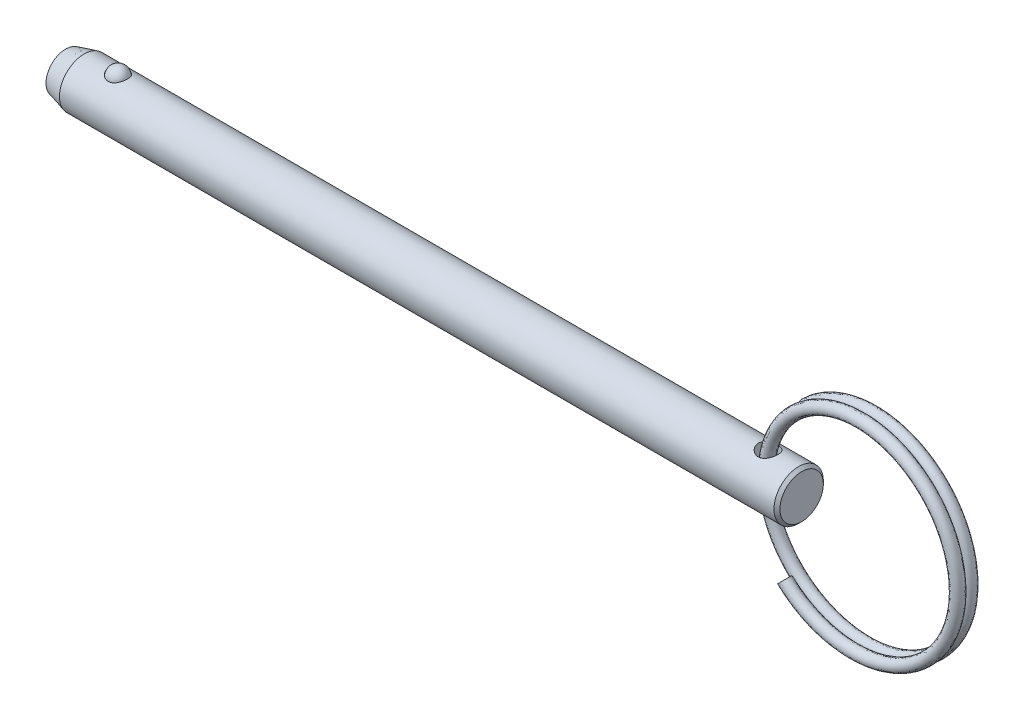
SolidWorks part; units mm, degrees
ref_plane "Front" through (0, 0, 0) normal (0, 0, 1) x (1, 0, 0)
ref_plane "Top" through (0, 0, 0) normal (0, 1, 0) x (1, 0, 0)
ref_plane "Right" through (0, 0, 0) normal (1, 0, 0) x (0, 0, -1)
sketch "Sketch1" plane through (0, 0, 0) normal (0, 0, 1) x (1, 0, 0)
  line L0 (5.588, 2.794) -> (5.207, 3.175)
  line L1 (5.207, 3.175) -> (5.588, 3.175) construction
  line L4 (5.588, 2.794) -> (5.588, 0)
  line L5 (5.588, 3.175) -> (5.588, 2.794) construction
  line L16 (5.207, 3.175) -> (-86.8349, 3.175)
  line L17 (-89.2048, 3.175) -> (-89.2048, 2.54) construction
  line L19 (-86.8349, 3.175) -> (-89.2048, 3.175) construction
  line L22 (-89.2048, -3.175) -> (-86.8349, -3.175) construction
  line L23 (-82.4703, 2.8575) -> (-82.4703, -2.8575) construction
  line L24 (-89.2048, 0) -> (5.588, 0)
  line L27 (5.588, 0) -> (8.382, 0) construction
  line L29 (-89.2048, 0) -> (-89.2048, -2.54) construction
  line L36 (0, 0) -> (0, 3.175) construction
  line L37 (-89.2048, 2.54) -> (-89.2048, 0)
  line L38 (-86.8349, -3.175) -> (5.588, -3.175) construction
  line L39 (-89.2048, -2.54) -> (-89.2048, -3.175) construction
  line L40 (-86.8349, 3.175) -> (-89.2048, 2.54)
  line L42 (-86.8349, -3.175) -> (-89.2048, -2.54) construction
  line L43 (-86.8349, 3.175) -> (-86.8349, -3.175) construction
  circle A2 centre (-82.4703, 2.8575) radius 1.2319 construction
  point P35 (-81.28, 3.175)
  dimension "D2" = 5.715
  dimension "D11" = 0.9144
  dimension "A" = 6.35
  dimension "D" = 5.588
  dimension "E" = 7.2644
  dimension "D3" = 0.381
  dimension "Useable Length" = 81.28
  dimension "D12" = 5.08
  dimension "C" = 7.9248
  dimension "A1" = 15
revolve "Revolve1" add sketch "Sketch1" angle 360 about L27
sketch "Sketch2" plane through (0, 0, 0) normal (0, 0, 1) x (1, 0, 0)
  line L0 (-81.213, 2.8575) -> (-83.7276, 2.8575)
  line L1 (-82.4703, 4.0894) -> (-82.4703, 4.1148) construction
  line L2 (-81.213, 2.8575) -> (-78.6984, 2.8575) construction
  circle A0 centre (-82.4703, 2.8575) radius 1.2319 construction
  circle A1 centre (-82.4703, 2.8575) radius 1.2319 construction
  arc A2 (-83.7276, 2.8575) -> (-81.213, 2.8575) centre (-82.4703, 2.8575) cw
  dimension "D1" = 0.0254
revolve "Cut-Revolve1" cut sketch "Sketch2" angle 360 about L2
sketch "Sketch3" plane through (0, 0, 0) normal (0, 0, 1) x (1, 0, 0)
  line L0 (-81.2384, 2.8575) -> (-83.7022, 2.8575)
  line L1 (-81.2384, 2.8575) -> (-78.7746, 2.8575) construction
  circle A0 centre (-82.4703, 2.8575) radius 1.2319 construction
  arc A1 (-81.2384, 2.8575) -> (-83.7022, 2.8575) centre (-82.4703, 2.8575) ccw
revolve "Revolve2" add sketch "Sketch3" angle 360 about L1
sketch "Sketch4" plane through (0, 0, 0) normal (0, 0, 1) x (1, 0, 0)
  line L1 (1.27, -3.175) -> (2.54, -3.175)
  line L2 (1.27, -3.175) -> (1.27, 3.175)
  line L3 (1.27, 3.175) -> (2.54, 3.175)
  line L4 (2.54, -3.175) -> (2.54, 3.175)
  line L5 (1.27, -3.175) -> (1.27, -4.445) construction
  line L6 (2.54, 3.175) -> (5.588, 3.175) construction
  line L8 (0, -3.175) -> (0, 3.175) construction
  line L9 (0, 0) -> (1.27, 0) construction
  line L11 (1.27, 0) -> (2.54, 0) construction
  line L12 (5.207, 3.175) -> (-86.8349, 3.175) construction
  line L14 (-86.8349, -3.175) -> (5.588, -3.175) construction
  dimension "D1" = 2.54
revolve "Cut-Revolve2" cut sketch "Sketch4" angle 360 about L2
sketch "Sketch5" plane through (0, 0, 0) normal (0, 0, 1) x (1, 0, 0)
  line L0 (0, 0) -> (0.293, 0) construction
  line L1 (0.293, 0) -> (0.293, 3.175) construction
  line L2 (5.207, 3.175) -> (-86.8349, 3.175) construction
  line L3 (13.755, 0) -> (27.217, 0) construction
  line L4 (2.54, 3.175) -> (2.247, 3.175) construction
  line L5 (1.27, 3.175) -> (2.54, 3.175) construction
  line L6 (0.6728, 3.175) -> (0.6728, -3.175) construction
  line L7 (0.293, 3.175) -> (0, 3.175) construction
  line L8 (1.27, -3.175) -> (2.54, -3.175) construction
  line L9 (0.6728, -3.175) -> (2.54, -3.175) construction
  line L10 (0.293, 0) -> (13.755, 0) construction
  line L11 (13.755, 0) -> (8.7098, -10.8195) construction
  line L12 (2.247, 3.175) -> (0.6728, 3.175) construction
  line L13 (13.755, 11.938) -> (13.755, 13.462) construction
  line L14 (8.7098, -10.8195) -> (8.3878, -11.5101) construction
  circle A0 centre (13.755, 0) radius 13.462
  circle A1 centre (13.755, 0) radius 11.938 construction
  circle A2 centre (13.755, 0) radius 12.7 construction
  point P26 (13.755, 12.7)
  dimension "D1" = 65
  dimension "R Ring Dia" = 25.4
  dimension "Ring OD" = 1.524
curve "Helix/Spiral1" pitch 1.5494 height 1.3557 radius 13.462 left hand yes centre (13.755, 0, 0) axis (0, 0, -1) start towards (1, 0, 0)
sketch "Sketch6" plane through (114.0038, 0, 0) normal (0, 1, 0) x (0, 0, -1)
  line L0 (0, 112.1868) -> (0, 112.9488) construction
  line L1 (0, 112.9488) -> (0, 113.7108) construction
  circle A0 centre (0, 112.9488) radius 0.762
  dimension "D1" = 1.524
sketch "Sketch7" plane through (0, 0, 0) normal (0, 0, 1) x (1, 0, 0)
  circle A0 centre (13.755, 0) radius 13.462 construction
  circle A1 centre (13.755, 0) radius 13.462
curve "Helix/Spiral2" pitch 1.5494 height 1.3557 radius 13.462 left hand yes centre (13.755, 0, 0) axis (0, 0, 1) start towards (1, 0, 0)
sweep "Sweep1" add profiles "Sketch6" path "Helix/Spiral1"
sweep "Sweep2" add profiles "Sketch6<2>" path "Helix/Spiral2"
sketch "Sketch6<2>" plane through (114.0038, 0, 0) normal (0, 1, 0) x (0, 0, -1) same geometry as "Sketch6"
ref_plane "Plane1" through (0, -10.8195, 0) normal (0, 1, 0) x (-1, 0, 0)
sketch "Sketch8" plane through (0, -10.8195, 0) normal (0, 1, 0) x (-1, 0, 0)
  line L0 (296.0902, 0) -> (-8.7098, 0) construction
  line L1 (10.3402, -0.7779) -> (4.5066, -0.7779)
  line L2 (3.5004, -0.9415) -> (-7.2005, -4.517)
  line L3 (-7.2005, 4.517) -> (3.5004, 0.9415)
  line L4 (4.5066, 0.7779) -> (282.8738, 0.7779)
  line L5 (283.88, 0.9415) -> (294.5809, 4.517)
  line L6 (277.0402, -0.7779) -> (282.8738, -0.7779)
  line L7 (283.88, -0.9415) -> (294.5809, -4.517)
  line L8 (10.3402, -0.7779) -> (10.3402, 0.7779) construction
  arc A0 (-7.2005, 4.517) -> (-7.2005, -4.517) centre (-8.7098, 0) ccw
  arc A1 (294.5809, -4.517) -> (294.5809, 4.517) centre (296.0902, 0) ccw
  arc A2 (4.5066, -0.7779) -> (3.5004, -0.9415) centre (4.5066, -3.9529) ccw
  arc A3 (3.5004, 0.9415) -> (4.5066, 0.7779) centre (4.5066, 3.9529) ccw
  arc A4 (282.8738, -0.7779) -> (283.88, -0.9415) centre (282.8738, -3.9529) cw
  arc A5 (282.8738, 0.7779) -> (283.88, 0.9415) centre (282.8738, 3.9529) ccw
  point P6 (10.3402, 0)
  point P16 (3.9902, -0.7779)
  point P20 (3.9902, 0.7779)
  point P23 (283.3902, -0.7779)
  point P26 (283.3902, 0.7779)
  dimension "D2" = 4.7625
  dimension "D3" = 1.5557
  dimension "D6" = 3.175
  dimension "Lanyard Length" = 304.8
  dimension "D4" = 6.35
  dimension "D5" = 12.7
ref_plane "Plane2" through (-10.3402, 0, 0) normal (1, 0, 0) x (0, 0, -1)
sketch "Sketch9" plane through (-10.3402, 0, 0) normal (1, 0, 0) x (0, 0, -1)
  circle A0 centre (0.7779, -10.8195) radius 0.7779
sweep "Sweep3" [suppressed] add profiles "Sketch9" path "Sketch8"
sketch "Sketch10" [suppressed] plane through (-10.3402, 0, 0) normal (1, 0, 0) x (0, 0, -1)
  arc A0 (-0.3849, -10.1482) -> (-0.3849, -11.4908) centre (-0.7779, -10.8195) ccw
  circle A1 centre (0.7779, -10.8195) radius 0.7779
  arc A2 (0.3849, -11.4908) -> (0.3849, -10.1482) centre (0.7779, -10.8195) ccw
  arc A3 (-0.3849, -11.4908) -> (0.3849, -11.4908) centre (0, -12.1485) cw
  arc A4 (-0.3869, -9.3301) -> (-0.3869, -12.3089) centre (-0.7779, -10.8195) ccw
  arc A5 (0.3869, -12.3089) -> (0.3869, -9.3301) centre (0.7779, -10.8195) ccw
  circle A6 centre (-0.7779, -10.8195) radius 1.5399 construction
  circle A7 centre (-0.7779, -10.8195) radius 0.7779 construction
  arc A8 (-0.3849, -10.1482) -> (0.3849, -10.1482) centre (0, -9.4905) ccw
  arc A9 (-0.3869, -9.3301) -> (0.3869, -9.3301) centre (0, -7.856) ccw
  arc A10 (0.3869, -12.3089) -> (-0.3869, -12.3089) centre (0, -13.783) ccw
  point P4 (-0.034, -10.2746)
  point P8 (2.3178, -10.502)
  point P9 (0.762, -10.502)
  dimension "D3" = 1.524
  dimension "D4" = 0.762
  dimension "D2" = 0.762
  dimension "D1" = 0
extrude "Extrude1" [suppressed] add sketch "Sketch10" along normal blind 5.715 separate body
sketch "Sketch11" [suppressed] plane through (-277.0402, 0, 0) normal (1, 0, 0) x (0, 0, -1)
  arc A4 (-0.3849, -10.1482) -> (-0.3849, -11.4908) centre (-0.7779, -10.8195) ccw
  arc A5 (0.3849, -11.4908) -> (-0.3849, -11.4908) centre (0, -12.1485) ccw
  arc A6 (0.3849, -11.4908) -> (0.3849, -10.1482) centre (0.7779, -10.8195) ccw
  arc A7 (-0.3849, -10.1482) -> (0.3849, -10.1482) centre (0, -9.4905) ccw
  arc A8 (-0.3849, -10.1482) -> (-0.3849, -11.4908) centre (-0.7779, -10.8195) ccw
  arc A9 (0.3849, -11.4908) -> (-0.3849, -11.4908) centre (0, -12.1485) ccw
  arc A10 (0.3849, -11.4908) -> (0.3849, -10.1482) centre (0.7779, -10.8195) ccw
  arc A11 (-0.3849, -10.1482) -> (0.3849, -10.1482) centre (0, -9.4905) ccw
  arc A12 (-0.3869, -9.3301) -> (-0.3869, -12.3089) centre (-0.7779, -10.8195) ccw
  arc A13 (0.3869, -12.3089) -> (-0.3869, -12.3089) centre (0, -13.783) ccw
  arc A14 (0.3869, -12.3089) -> (0.3869, -9.3301) centre (0.7779, -10.8195) ccw
  arc A15 (-0.3869, -9.3301) -> (0.3869, -9.3301) centre (0, -7.856) ccw
  arc A16 (-0.3869, -9.3301) -> (-0.3869, -12.3089) centre (-0.7779, -10.8195) ccw
  arc A17 (0.3869, -12.3089) -> (-0.3869, -12.3089) centre (0, -13.783) ccw
  arc A18 (0.3869, -12.3089) -> (0.3869, -9.3301) centre (0.7779, -10.8195) ccw
  arc A19 (-0.3869, -9.3301) -> (0.3869, -9.3301) centre (0, -7.856) ccw
  dimension "D1" = 0
  dimension "D2" = 0
extrude "Extrude2" [suppressed] add sketch "Sketch11" against normal blind 5.715 separate body
sketch "Sketch12" plane through (0, -10.8195, 0) normal (0, 1, 0) x (-1, 0, 0)
  line L0 (326.8712, -5.2864) -> (321.3086, -5.2864) construction
  line L1 (326.8712, -5.9214) -> (310.5026, -5.9214)
  line L2 (326.8712, -5.9214) -> (326.8712, -4.6514)
  line L3 (326.8712, -4.6514) -> (310.7265, -4.6514)
  line L4 (310.5026, -5.9214) -> (310.7265, -4.6514) construction
  line L5 (310.5026, -5.9214) -> (295.1212, -0.3231)
  line L6 (321.3086, -5.2864) -> (310.6146, -5.2864) construction
  line L7 (310.7265, -4.6514) -> (295.5555, 0.8704)
  line L8 (295.1212, -0.3231) -> (295.5555, 0.8704)
  line L9 (310.6146, -5.2864) -> (300.5655, -1.6289) construction
  line L10 (300.5655, -1.6289) -> (295.3383, 0.2737) construction
  arc A0 (294.5809, -4.517) -> (294.5809, 4.517) centre (296.0902, 0) ccw construction
  dimension "D1" = 20
  dimension "D2" = 31.75
  dimension "D3" = 1.27
  dimension "D4" = 5.5626
extrude "Extrude3" [suppressed] add sketch "Sketch12" along normal mid plane 12.7 separate body
sketch "Sketch13" [suppressed] plane through (0, 0, -4.6514) normal (0, 0, 1) x (1, 0, 0)
  line L0 (-326.8712, -10.8195) -> (-310.7265, -10.8195) construction
  line L1 (-324.8782, -4.4695) -> (-326.8712, -4.4695)
  line L2 (-326.8712, -4.4695) -> (-310.7265, -4.4695) construction
  line L3 (-326.8712, -4.4695) -> (-328.8642, -4.4695)
  line L4 (-328.8642, -4.4695) -> (-328.8642, -17.1695)
  line L5 (-328.8642, -17.1695) -> (-326.8712, -17.1695)
  line L6 (-326.8712, -17.1695) -> (-324.8782, -17.1695)
  line L7 (-326.8712, -17.1695) -> (-310.7265, -17.1695) construction
  arc A0 (-324.8782, -4.4695) -> (-324.8782, -17.1695) centre (-315.7587, -10.8195) ccw
  circle A1 centre (-321.3086, -10.8195) radius 2.5781
  dimension "D1" = 5.1562
  dimension "D2" = 11.1125
extrude "Extrude4" [suppressed] cut sketch "Sketch13" against normal up to surface (1.27 mm away)
sketch "Sketch14" [suppressed] plane through (-34.8532, 0, 95.7583) normal (-0.342, 0, 0.9397) x (0.9397, 0, 0.342)
  line L3 (-279.4267, -4.4695) -> (-277.4337, -4.4695)
  line L4 (-277.4337, -4.4695) -> (-275.4407, -4.4695)
  line L5 (-275.4407, -4.4695) -> (-275.4407, -17.1695)
  line L6 (-275.4407, -17.1695) -> (-277.4337, -17.1695)
  line L7 (-277.4337, -17.1695) -> (-279.4267, -17.1695)
  line L8 (-277.4337, -4.4695) -> (-277.4337, -17.1695) construction
  line L9 (-293.5783, -4.4695) -> (-277.4337, -4.4695) construction
  line L10 (-293.6903, -10.8195) -> (-282.9963, -10.8195) construction
  arc A0 (-279.4267, -17.1695) -> (-279.4267, -4.4695) centre (-288.5462, -10.8195) ccw
  circle A1 centre (-282.9963, -10.8195) radius 2.5781
  dimension "D1" = 5.1562
  dimension "D2" = 11.1125
extrude "Extrude6" [suppressed] cut sketch "Sketch14" against normal up to surface (1.27 mm away)
sketch "Sketch15" [suppressed] plane through (0, 0, 0) normal (0, 0, 1) x (1, 0, 0)
  line L1 (-257.8086, -4.4695) -> (-99.0586, -4.4695)
  line L2 (-257.8086, -4.4695) -> (-270.5086, -17.1695)
  line L3 (-270.5086, -17.1695) -> (-111.7586, -17.1695)
  line L4 (-99.0586, -4.4695) -> (-111.7586, -17.1695)
  line L5 (-324.8782, -4.4695) -> (-310.7265, -4.4695) construction
  line L6 (-324.8782, -17.1695) -> (-310.7265, -17.1695) construction
  circle A0 centre (-321.3086, -10.8195) radius 2.5781 construction
  dimension "D1" = 63.5
  dimension "D2" = 158.75
  dimension "D3" = 45
extrude "Extrude7" [suppressed] cut sketch "Sketch15" against normal through all and the other way through all
move or copy body "Body-Move/Copy1" [suppressed] bodies to move or copy 147 151 144 copy no translate (152.4, 0, 0)
sketch "Sketch16" [suppressed] plane through (0, 0, 0) normal (0, 0, 1) x (1, 0, 0)
  line L0 (-111.7586, -6.057) -> (-111.7586, -9.232) construction
  line L1 (-111.7586, -9.232) -> (-109.2186, -8.2795) construction
  line L2 (-109.2186, -8.2795) -> (-114.2986, -13.3595) construction
  line L3 (-114.2986, -13.3595) -> (-111.7586, -12.407) construction
  line L4 (-111.7586, -12.407) -> (-111.7586, -15.582) construction
  line L5 (-112.5364, -11.5974) -> (-110.9807, -10.0416) construction
  line L6 (-105.4086, -15.582) -> (-105.4086, -12.407) construction
  line L7 (-105.4086, -12.407) -> (-107.9486, -13.3595) construction
  line L8 (-107.9486, -13.3595) -> (-102.8686, -8.2795) construction
  line L9 (-102.8686, -8.2795) -> (-105.4086, -9.232) construction
  line L10 (-105.4086, -9.232) -> (-105.4086, -6.057) construction
  line L11 (-104.6307, -10.0416) -> (-106.1864, -11.5974) construction
  line L14 (-4.5066, -10.8195) -> (-282.8738, -10.8195) construction
  dimension "D1" = 3.175
  dimension "D2" = 3.175
  dimension "D3" = 5.08
  dimension "D4" = 1.5875
equation "\"D12@Sketch1\"=\"A@Sketch1\" * 0.80"
equation "\"D2@Sketch1\"=\"A@Sketch1\" * 0.9"
equation "\"D1@Sketch4\" = \"A@Sketch1\" / 2.5"
equation "\"Ring OD@Sketch5\" = \"R Ring Dia@Sketch5\" * 0.06"
equation "\"D4@Helix/Spiral1\"=\"Ring OD@Sketch5\" + 0.001"
equation "\"D1@Sketch6\"=\"Ring OD@Sketch5\""
equation "\"D4@Helix/Spiral2\" = \"D4@Helix/Spiral1\""
equation "\"D5@Helix/Spiral2\" = \"D5@Helix/Spiral1\""
equation "\"D1@Sketch14\" = \"D1@Sketch13\""
equation "\"D2@Sketch14\" = \"D2@Sketch13\""
